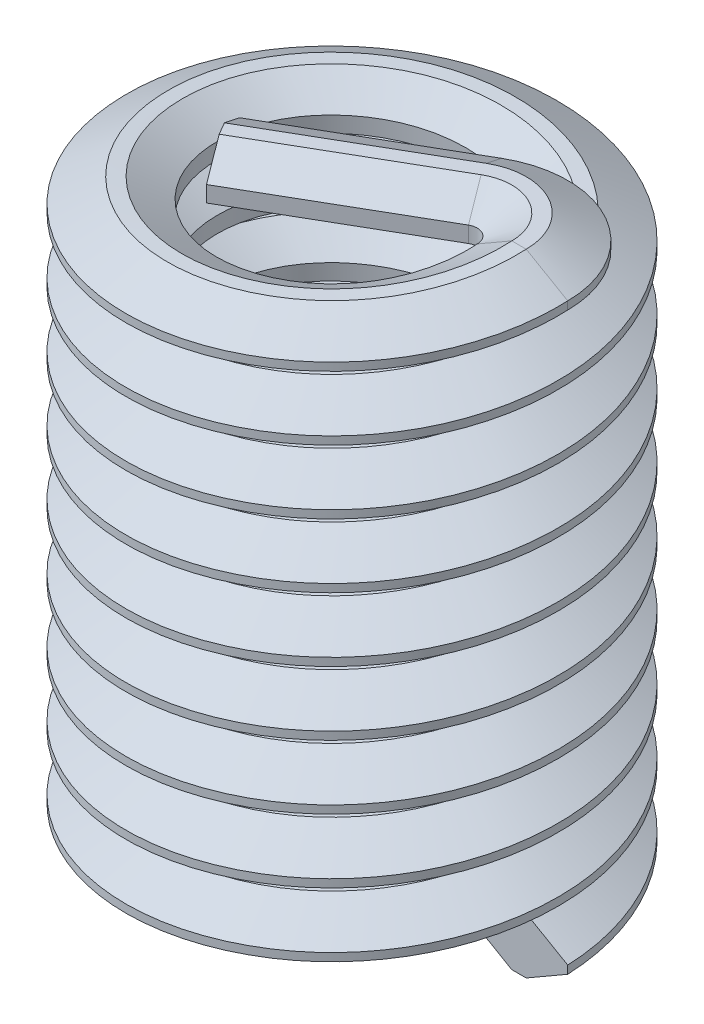
SolidWorks part; units mm, degrees
ref_plane "Front Plane" through (0, 0, 0) normal (0, 0, 1) x (1, 0, 0)
ref_plane "Top Plane" through (0, 0, 0) normal (0, 1, 0) x (1, 0, 0)
ref_plane "Right Plane" through (0, 0, 0) normal (1, 0, 0) x (0, 0, -1)
sketch "Sketch1" plane through (0, 0, 0) normal (0, 0, 1) x (-1, 0, 0)
  line L0 (0, 0) -> (0, 9.525) construction
  line L1 (-0.6969, 0) -> (-1.0433, 0.2) construction
  line L2 (-1.0469, 0.2) -> (-1.3933, 0) construction
  line L3 (-1.3933, 0) -> (-1.0469, -0.2) construction
  line L4 (-1.0433, -0.2) -> (-0.6969, 0) construction
  line L5 (-1.0433, -0.2) -> (-1.0433, 0.2) construction
  line L6 (-0.6969, 0) -> (0, 0) construction
  line L8 (-1.35, -0.025) -> (-1.0902, -0.175)
  line L9 (-1, -0.175) -> (-0.7835, -0.05)
  line L10 (-0.7402, -0.025) -> (-0.7402, 0.025) construction
  line L11 (-0.7835, 0.05) -> (-1, 0.175)
  line L12 (-1.0902, 0.175) -> (-1.35, 0.025)
  line L13 (-0.6969, 0) -> (-0.7402, 0) construction
  line L14 (-0.7402, 0) -> (-1, 0) construction
  line L15 (-1.0902, 0) -> (-1.35, 0) construction
  line L16 (-1.35, 0) -> (-1.3933, 0) construction
  line L17 (-1.0902, 0.175) -> (-1, 0.175)
  line L18 (-1, 0.175) -> (-1, -0.175) construction
  line L19 (-1, -0.175) -> (-1.0902, -0.175)
  line L20 (-1.0902, -0.175) -> (-1.0902, 0.175) construction
  line L21 (-1.0902, 0) -> (-1.0433, 0) construction
  line L22 (-1.0433, 0) -> (-1, 0) construction
  line L23 (-1.35, 0.2) -> (-1.35, -3.8) construction
  line L24 (-0.7835, -0.05) -> (-0.7835, 0.05)
  line L25 (-0.7835, 0) -> (-0.7402, 0) construction
  line L26 (-1.35, -0.025) -> (-1.35, 0.025)
  line L28 (1.35, 0.2) -> (1.35, -3.8) construction
  line L29 (-1.0433, -0.2) -> (-1.0469, -0.2) construction
  line L31 (-1.0469, 0.2) -> (-1.0433, 0.2) construction
  dimension "D3" = 0.4
  dimension "D4" = 0.05
  dimension "Installed Length" = 4
  dimension "Thread Size" = 2
  dimension "Max OD" = 2.7
sketch "Sketch2" plane through (0, 0, 0) normal (0, 1, 0) x (1, 0, 0)
  circle A0 centre (0, 0) radius 1
curve "Helix/Spiral1" pitch 0.4 height 3.6 radius 1 centre (0, 0, 0) axis (0, 1, 0) start towards (1, 0, 0) parameters "Height"=3.6, "Pitch"=0.4
sweep "Sweep1" add profiles "Sketch1" path "Helix/Spiral1"
sketch "Sketch3" plane through (0, 0, 0) normal (0, 0, -1) x (-1, 0, 0)
  line L0 (-5.4053, 0.8816) -> (-0.6969, 3.6) construction
  line L1 (-8.3368, 8.0109) -> (-0.6969, 3.6) construction
  line L2 (-0.6969, 3.6) -> (-0.6969, 3.7) construction
  line L8 (-1, 3.425) -> (-0.7835, 3.55)
  line L9 (-0.7835, 3.55) -> (-0.7835, 3.65)
  line L10 (-0.7835, 3.65) -> (-1, 3.775)
  line L12 (-1.0902, 3.775) -> (-1.35, 3.625)
  line L13 (-1.35, 3.625) -> (-1.35, 3.575)
  line L14 (-1.35, 3.575) -> (-1.0902, 3.425)
  line L16 (-1, 3.425) -> (-0.7835, 3.55)
  line L17 (-0.7835, 3.55) -> (-0.7835, 3.65)
  line L18 (-0.7835, 3.65) -> (-1, 3.775)
  line L20 (-1.0902, 3.775) -> (-1.35, 3.625)
  line L21 (-1.35, 3.625) -> (-1.35, 3.575)
  line L22 (-1.35, 3.575) -> (-1.0902, 3.425)
  line L23 (-1, 3.775) -> (-1.0902, 3.775)
  line L24 (-1, 3.775) -> (-1.0902, 3.775)
  line L25 (-1.0902, 3.425) -> (-1, 3.425)
  line L26 (-1.0902, 3.425) -> (-1, 3.425)
  dimension "D1" = 0
revolve "Revolve1" add sketch "Sketch3" angle 120 about L2
sketch "Sketch4" plane through (0.5227, 0, -0.3018) normal (-0.866, 0, 0.5) x (0.5, 0, 0.866)
  line L8 (-0.0449, 3.425) -> (0.0453, 3.425)
  line L9 (0.0453, 3.425) -> (0.2618, 3.55)
  line L10 (0.2618, 3.55) -> (0.2618, 3.65)
  line L11 (0.2618, 3.65) -> (0.0453, 3.775)
  line L12 (-0.0449, 3.425) -> (0.0453, 3.425)
  line L13 (-0.0449, 3.775) -> (-0.3047, 3.625)
  line L14 (-0.3047, 3.625) -> (-0.3047, 3.575)
  line L15 (-0.3047, 3.575) -> (-0.0449, 3.425)
  line L17 (0.0453, 3.425) -> (0.2618, 3.55)
  line L18 (0.2618, 3.55) -> (0.2618, 3.65)
  line L19 (0.2618, 3.65) -> (0.0453, 3.775)
  line L21 (-0.0449, 3.775) -> (-0.3047, 3.625)
  line L22 (-0.3047, 3.625) -> (-0.3047, 3.575)
  line L23 (-0.3047, 3.575) -> (-0.0449, 3.425)
  spline S4 degree 1 poles (3000.0295, 3.775) (-3000.0216, 3.775) knots -33262.057828 -33262.057828 33262.976537 33262.976537 only from (0.0453, 3.775) to (-0.0449, 3.775)
  spline S5 degree 1 poles (0.0453, 3.775) (-0.0449, 3.775) knots 0 0 1 1
  dimension "D1" = 0
extrude "Extrude1" add sketch "Sketch4" along normal blind 1.2
equation "\"D3@Sketch1\" = \"Pitch@Helix/Spiral1\""
equation "\"D4@Sketch1\" = \"D3@Sketch1\"  * 1 / 8"
equation "\"D1@Extrude1\" = \"Thread Size@Sketch1\" * 0.6"
equation "\"Height@Helix/Spiral1\" = \"Installed Length@Sketch1\" - \"Pitch@Helix/Spiral1\""
